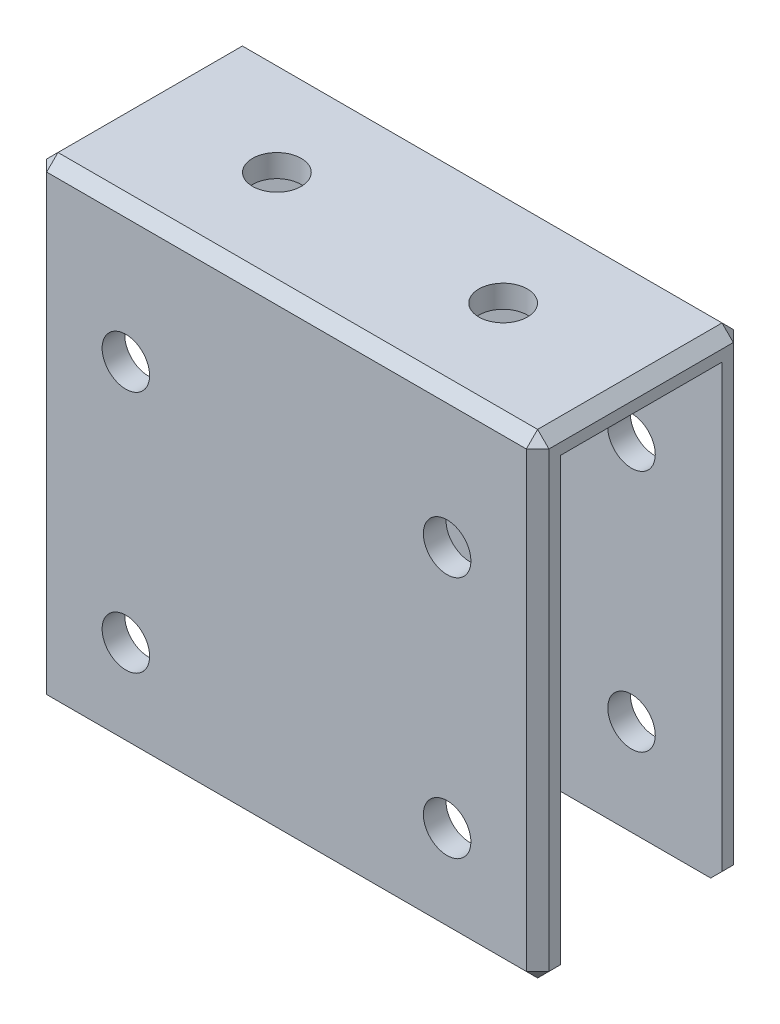
SolidWorks part; units mm, degrees
ref_plane "Front Plane" through (0, 0, 0) normal (0, 0, 1) x (1, 0, 0)
ref_plane "Top Plane" through (0, 0, 0) normal (0, 1, 0) x (1, 0, 0)
ref_plane "Right Plane" through (0, 0, 0) normal (1, 0, 0) x (0, 0, -1)
sketch "Sketch1" plane through (0, 0, 0) normal (0, 0, 1) x (1, 0, 0)
  line L0 (22.2, 40) -> (22.2, 0) construction
  line L1 (0, 0) -> (44.4, 0)
  line L2 (0, 0) -> (0, 40)
  line L3 (0, 40) -> (44.4, 40)
  line L4 (44.4, 0) -> (44.4, 40)
  line L5 (0, 0) -> (8, 0) construction
  line L6 (0, 0) -> (0, 8) construction
  line L10 (8, 29.9769) -> (8, 27.8769) construction
  line L11 (8, 19) -> (8, 8.4769) construction
  line L12 (8, 19) -> (10.573, 19) construction
  line L15 (10.573, 19) -> (10.573, 40) construction
  line L16 (8, 8.4769) -> (36.4, 8.4769) construction
  line L17 (36.4, 8.4769) -> (36.4, 29.9769) construction
  circle A0 centre (8, 8.4769) radius 2.1
  circle A1 centre (8, 29.9769) radius 2.1
  circle A2 centre (36.4, 29.9769) radius 2.1
  circle A3 centre (36.4, 8.4769) radius 2.1
  dimension "D5" = 4.2
  dimension "D6" = 4.2
  dimension "D7" = 4.2
  dimension "D8" = 4.2
  dimension "D1" = 44.4
  dimension "D2" = 40
  dimension "D3" = 21.5
  dimension "D4" = 21.5
  dimension "D9" = 21
  dimension "D10" = 8
  dimension "D11" = 8
extrude "Boss-Extrude1" add sketch "Sketch1" along normal blind 2
sketch "Sketch2" plane through (0, 40, 0) normal (0, 1, 0) x (1, 0, 0)
  line L0 (44.4, -2) -> (44.4, 0) construction
  line L1 (0, -2) -> (44.4, -2)
  line L2 (0, -2) -> (0, 16.3)
  line L3 (0, 16.3) -> (44.4, 16.3)
  line L4 (44.4, -2) -> (44.4, 16.3)
  dimension "D1" = 18.3
  dimension "D2" = 44.4
extrude "Boss-Extrude2" add sketch "Sketch2" along normal blind 2
pattern_linear "LPattern1" count 2 spacing 16.3 along (0, 0, -1) of "Boss-Extrude1"
sketch "Sketch3" plane through (0, 42, 0) normal (0, 1, 0) x (1, 0, 0)
  line L0 (22.2, 16.3) -> (22.2, -2) construction
  line L1 (44.4, 16.3) -> (0, 16.3) construction
  line L2 (0, -2) -> (44.4, -2) construction
  line L3 (22.2, 7.15) -> (12.2, 7.15) construction
  line L4 (22.2, 7.15) -> (32.2, 7.15) construction
  circle A0 centre (12.2, 7.15) radius 2.15
  circle A1 centre (32.2, 7.15) radius 2.15
  dimension "D3" = 4.3
  dimension "D4" = 4.3
  dimension "D1" = 10
  dimension "D2" = 10
extrude "Cut-Extrude1" cut sketch "Sketch3" against normal through all
chamfer "Chamfer1" distance 1 angle 45 14 edges at (22.2, 42, -16.3) (0, 42, -7.15) (0, 21, -16.3) (22.2, 42, 2) (0, 21, 2) (0, 0, -15.3) (0, 0, 1) (22.2, 0, 2) (44.4, 0, 1) (44.4, 21, 2) (44.4, 42, -7.15) (44.4, 21, -16.3) (44.4, 0, -15.3) (22.2, 0, -16.3)
